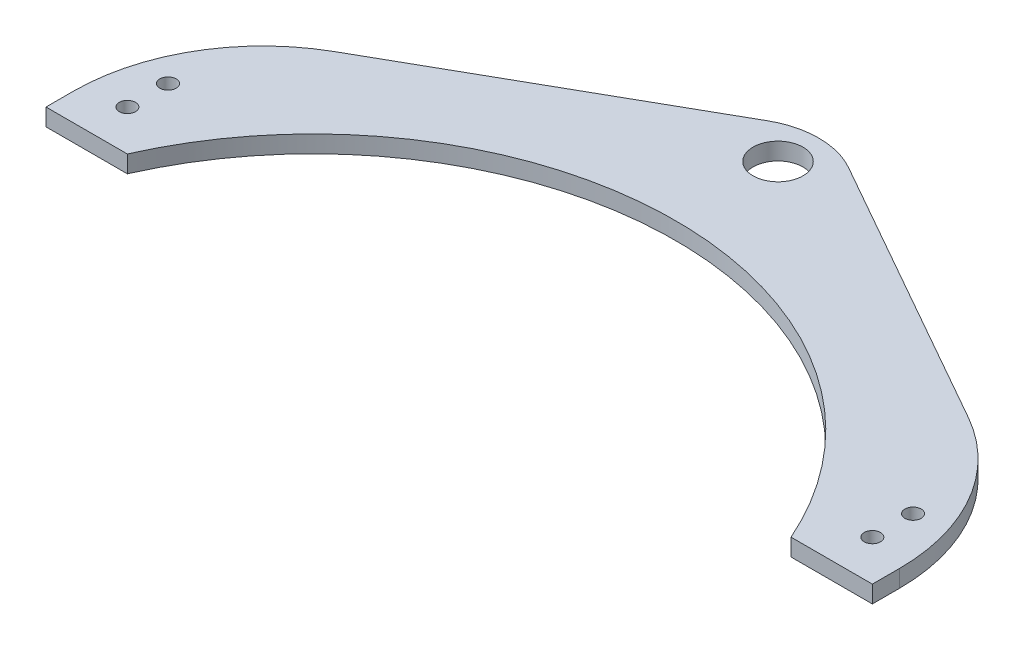
SolidWorks part; units mm, degrees
ref_plane "Front Plane" through (0, 0, 0) normal (0, 0, 1) x (1, 0, 0)
ref_plane "Top Plane" through (0, 0, 0) normal (0, 1, 0) x (1, 0, 0)
ref_plane "Right Plane" through (0, 0, 0) normal (1, 0, 0) x (0, 0, -1)
sketch "Sketch1" plane through (0, 0, 0) normal (0, 1, 0) x (1, 0, 0)
  line L0 (0, 0) -> (122.4, 0)
  line L1 (61.2, 0) -> (61.2, 39.9)
  line L2 (122.4, 0) -> (137.4, 0)
  line L3 (0, 0) -> (-15, 0)
  line L4 (137.4, 0) -> (137.4, 16.6577)
  line L5 (-15, 0) -> (-15, 16.6577)
  line L6 (61.2, 0) -> (61.2, 58.8)
  line L7 (61.2, 58.8) -> (61.2, 66.3)
  line L8 (61.2, 66.3) -> (61.2465, 66.3)
  line L9 (61.2, 66.3) -> (61.1535, 66.3)
  line L10 (68.6399, 64.3514) -> (129.7934, 29.709)
  line L11 (53.7601, 64.3514) -> (-7.3934, 29.709)
  line L12 (129.9, 0) -> (129.9, 7.5)
  line L13 (129.9, 7.5) -> (129.9, 15)
  line L14 (-7.5, 0) -> (-7.5, 15)
  line L15 (119.6512, 35.4544) -> (68.6399, 64.3514)
  line L16 (137.4, 5.0012) -> (137.4, 0)
  line L17 (53.7601, 64.3514) -> (2.7488, 35.4544)
  line L18 (-15, 5.0012) -> (-15, 0)
  arc A0 (0, 0) -> (122.4, 0) centre (61.2, -26.9726) cw
  circle A1 centre (61.2, 58.8) radius 4.6
  arc A2 (61.2465, 66.3) -> (68.6399, 64.3514) centre (61.2465, 51.3) cw
  arc A3 (61.1535, 66.3) -> (53.7601, 64.3514) centre (61.1535, 51.3) ccw
  arc A4 (-15, 16.6577) -> (-7.3934, 29.709) centre (0, 16.6577) cw
  arc A5 (137.4, 16.6577) -> (129.7934, 29.709) centre (122.4, 16.6577) ccw
  circle A6 centre (129.9, 15) radius 1.5
  circle A7 centre (129.9, 7.5) radius 1.5
  circle A8 centre (-7.5, 15) radius 1.5
  circle A9 centre (-7.5, 7.5) radius 1.5
  arc A10 (119.6512, 35.4544) -> (137.4, 5.0012) centre (102.4, 5.0012) cw
  arc A11 (2.7488, 35.4544) -> (-15, 5.0012) centre (20, 5.0012) ccw
  point P17 (65.2, 66.3)
  point P20 (57.2, 66.3)
  point P23 (-15, 25.4)
  point P26 (137.4, 25.4)
  point P41 (137.4, 25.4)
  point P44 (-15, 25.4)
  dimension "D8" = 7.5
  dimension "D11" = 15
  dimension "D12" = 15
  dimension "D15" = 15
  dimension "D16" = 35
  dimension "D1" = 122.4
  dimension "D2" = 39.9
  dimension "D3" = 15
  dimension "D4" = 15
  dimension "D5" = 25.4
  dimension "D6" = 25.4
  dimension "D7" = 58.8
  dimension "D9" = 4
  dimension "D10" = 4
  dimension "D13" = 7.5
  dimension "D14" = 7.5
extrude "Boss-Extrude2" add sketch "Sketch1" along normal blind 3.175 contours L11 A11 L5 L3 A9 A8 A0 L6 A1 L7 L9 A3 | A10 L10 A2 L8 L7 A1 L6 A0 L2 A7 A6 L4 region at (21.8428, 0, -33.5229) region at (100.5572, 0, -33.5229)
